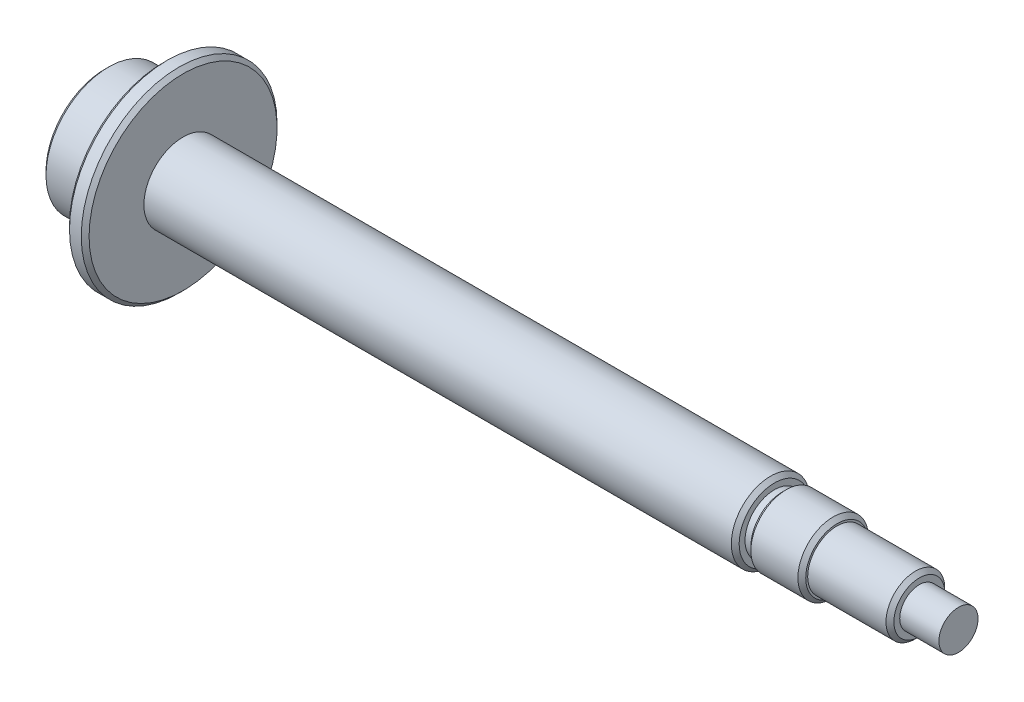
SolidWorks part; units mm, degrees
ref_plane "Спереди" through (0, 0, 0) normal (0, 0, 1) x (1, 0, 0)
ref_plane "Сверху" through (0, 0, 0) normal (0, 1, 0) x (1, 0, 0)
ref_plane "Справа" through (0, 0, 0) normal (1, 0, 0) x (0, 0, -1)
other "Configuration Table"
sketch "Эскиз1" plane through (0, 0, 0) normal (0, 0, 1) x (1, 0, 0)
  line L0 (0, 0) -> (0, 15)
  line L1 (1, 16) -> (15, 16)
  line L2 (15, 16) -> (15, 24)
  line L3 (16, 25) -> (19, 25)
  line L4 (20, 24) -> (20, 10)
  line L5 (20, 10) -> (170, 10)
  line L7 (174, 9) -> (186, 9)
  line L8 (187, 8) -> (187, 7.5)
  line L9 (187, 7.5) -> (207, 7.5)
  line L10 (208, 6.5) -> (208, 5)
  line L11 (208, 5) -> (218, 5)
  line L12 (218, 4) -> (218, 0)
  line L14 (0, 0) -> (225.6844, 0) construction
  line L15 (0, 0) -> (218, 0)
  line L16 (171, 9) -> (171, 7.5)
  line L17 (171, 7.5) -> (173, 7.5)
  line L18 (173, 7.5) -> (173, 8)
  line L19 (170, 10) -> (171, 9)
  line L20 (173, 8) -> (174, 9)
  line L21 (186, 9) -> (187, 8)
  line L22 (207, 7.5) -> (208, 6.5)
  line L23 (218, 5) -> (218, 4)
  line L24 (15, 24) -> (16, 25)
  line L25 (0, 15) -> (1, 16)
  line L26 (19, 25) -> (20, 24)
  point P1 (0, 16)
  point P5 (15, 25)
  point P6 (20, 25)
  point P8 (225.6844, 0)
  point P10 (187, 9)
  point P12 (208, 7.5)
  point P14 (218, 5)
  point P17 (171, 10)
  point P21 (173, 9)
  dimension "D1" = 32
  dimension "D2" = 50
  dimension "D3" = 15
  dimension "D4" = 5
  dimension "D5" = 20
  dimension "D6" = 18
  dimension "D7" = 15
  dimension "D8" = 10
  dimension "D9" = 151
  dimension "D10" = 2
  dimension "D11" = 21
  dimension "D12" = 10
  dimension "D13" = 15
  dimension "D14" = 14
revolve "Повернуть1" add sketch "Эскиз1" angle 360 about L14
cosmetic thread "Условное изображение резьбы2"
hole_wizard "Отверстие обработанное метчиком M101" positions "Эскиз4" profile "Эскиз3" tap size "M10" standard "DIN"
sketch "Эскиз4" plane through (0, 0, 0) normal (-1, 0, 0) x (0, 0, 1)
  point P0 (0, 0)
sketch "Эскиз3" plane through (0, 0, 0) normal (0, 1, 0) x (0, 0, 1)
  line L0 (0, 0) -> (0, 27.5)
  line L1 (0, 27.5) -> (4.25, 24.9463)
  line L2 (4.25, 24.9463) -> (4.25, 0.775)
  line L3 (4.25, 0.775) -> (5.025, 0)
  line L5 (5.025, 0) -> (0, 0)
  line L6 (-4.25, 0.775) -> (-5.025, 0) construction
  line L10 (0, 27.5) -> (-4.25, 24.9463) construction
  line L11 (0, -6.35) -> (0, 107.95) construction
  dimension "Диаметр сверла" = 8.5
  dimension "Глубина сверла" = 27.5
  dimension "Диаметр передней зенковки" = 10.05
  dimension "Угол передней зенковки" = 90
  dimension "Угол заточки сверла" = 118
cosmetic thread "Отверстие резьбы1"
